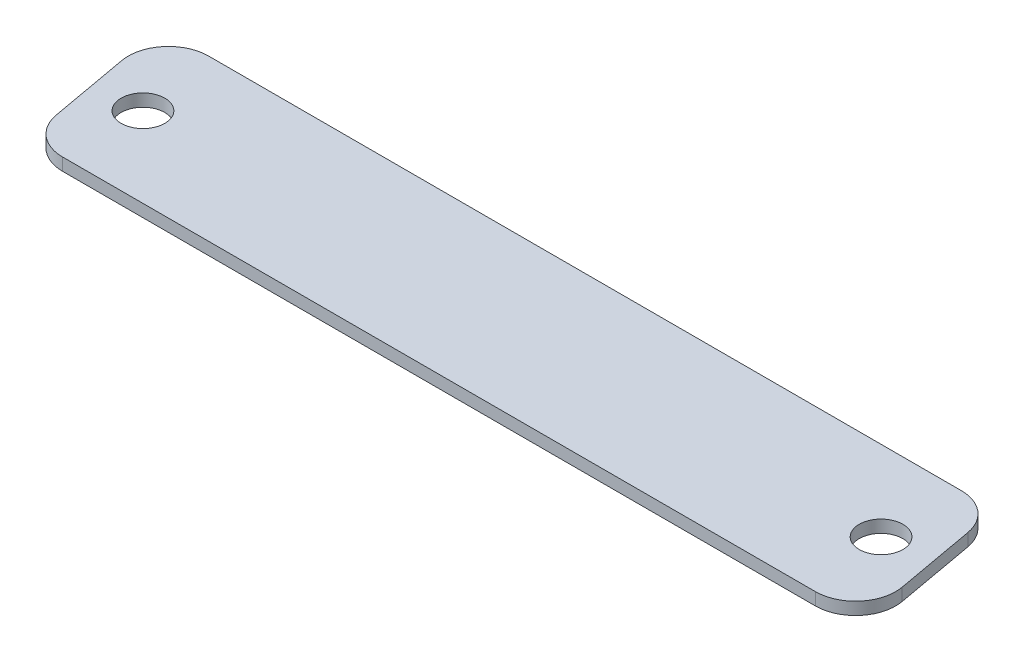
SolidWorks part; units mm, degrees
ref_plane "Front Plane" through (0, 0, 0) normal (0, 0, 1) x (1, 0, 0)
ref_plane "Top Plane" through (0, 0, 0) normal (0, 1, 0) x (1, 0, 0)
ref_plane "Right Plane" through (0, 0, 0) normal (1, 0, 0) x (0, 0, -1)
sketch "Sketch1" plane through (0, 0, 0) normal (0, 1, 0) x (1, 0, 0)
  line L3 (0, 0) -> (58.6486, 0)
  line L4 (0, 0) -> (0, 10.16)
  line L5 (0, 10.16) -> (58.6486, 10.16)
  line L6 (58.6486, 0) -> (58.6486, 10.16)
  dimension "D1" = 10.16
sheet metal parameters "Sheet-Metal1" thickness 0.7874 parameters "D1"=0.7366
base flange "Base-Flange1" sketch "Sketch1" thickness 0.7874 reverse thickness direction no parameters "D1"=0.7366
sketch "Sketch3" plane through (0, -0.7874, 0) normal (0, -1, 0) x (1, 0, 0)
  circle A0 centre (51.4405, -5.08) radius 1.9939 construction
  circle A1 centre (4.6979, -5.08) radius 1.9939 construction
  circle A2 centre (51.4405, -5.08) radius 1.9939 construction
  circle A3 centre (4.6979, -5.08) radius 1.9939 construction
  circle A4 centre (51.4405, -5.08) radius 1.3843
  circle A5 centre (4.6979, -5.08) radius 1.3843
  dimension "D1" = 2.7686
extrude "Cut-Extrude1" cut sketch "Sketch3" against normal through all normal cut yes
sketch "Sketch4" plane through (0, -0.7874, 0) normal (0, -1, 0) x (1, 0, 0)
  line L0 (59.4275, 22.2943) -> (48.5774, -37.8473) construction
  line L1 (-1.4325, -22.163) -> (7.0896, 25.0744) construction
  line L2 (59.4275, 22.2943) -> (48.5774, -37.8473) construction
  line L3 (-1.4325, -22.163) -> (7.0896, 25.0744) construction
  line L4 (53.5724, -10.16) -> (58.6486, -10.16)
  line L5 (58.6486, -10.16) -> (0, -10.16) construction
  line L6 (58.6486, -10.16) -> (58.6486, 0)
  line L7 (58.6486, 0) -> (55.4054, 0)
  line L8 (0, 0) -> (58.6486, 0) construction
  line L9 (55.4054, 0) -> (53.5724, -10.16)
  line L10 (0.733, -10.16) -> (0, -10.16)
  line L11 (0, -10.16) -> (0, 0)
  line L12 (0, 0) -> (2.5659, 0)
  line L13 (0.733, -10.16) -> (2.5659, 0)
extrude "Cut-Extrude2" cut sketch "Sketch4" against normal through all normal cut yes
fillet "Fillet1" radius 2.54 4 edges at (2.5659, -0.3937, 0) (0.733, -0.3937, -10.16) (53.5724, -0.3937, -10.16) (55.4054, -0.3937, 0)
flat pattern "Flat-Pattern1" [suppressed]
sketch "Bend-Lines1" plane through (0, 0, 0) normal (0, 1, 0) x (1, 0, 0)
sketch3d "Bounding-Box1" [suppressed]
  line L0 (-59.6628, 15.8364, 0) -> (0, 15.8364, 0) construction
  line L1 (-59.6628, 0, 0) -> (0, 0, 0) construction
  line L2 (-59.6628, 15.8364, 0) -> (-59.6628, 0, 0) construction
  line L3 (0, 15.8364, 0) -> (0, 0, 0) construction
